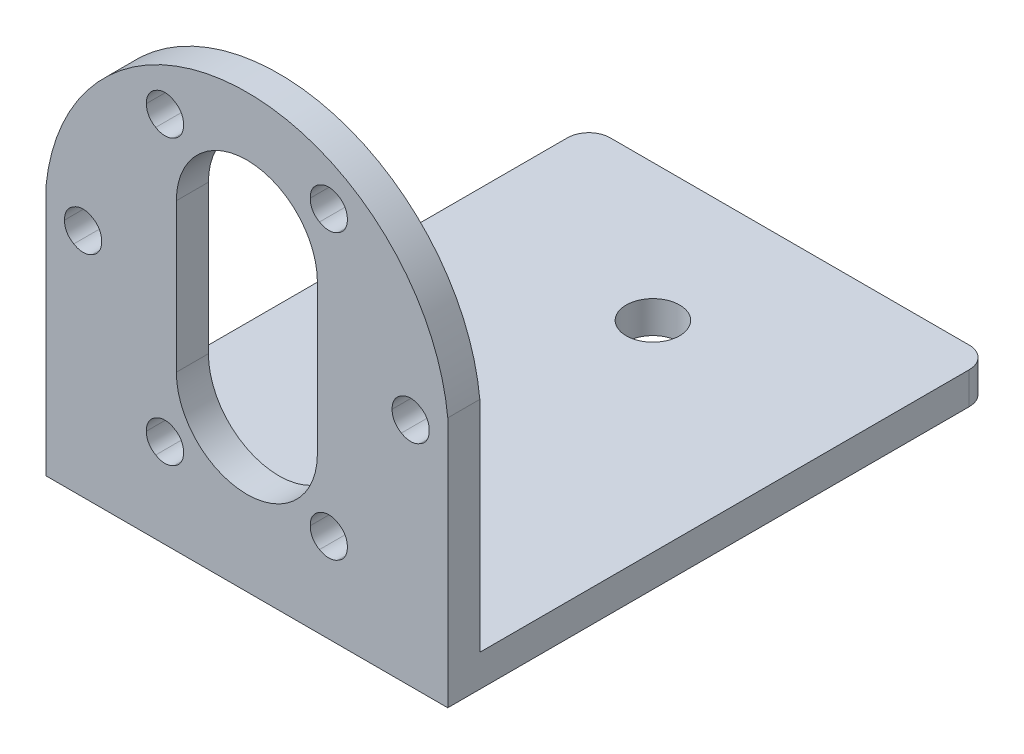
SolidWorks part; units mm, degrees
ref_plane "Front Plane" through (0, 0, 0) normal (0, 0, 1) x (1, 0, 0)
ref_plane "Top Plane" through (0, 0, 0) normal (0, 1, 0) x (1, 0, 0)
ref_plane "Right Plane" through (0, 0, 0) normal (1, 0, 0) x (0, 0, -1)
sketch "Sketch1" plane through (0, 0, 0) normal (0, 0, 1) x (1, 0, 0)
  line L0 (0, 0) -> (0, 39) construction
  line L1 (-18.8, 0) -> (18.8, 0)
  line L2 (-18.8, 0) -> (-18.8, 22)
  line L4 (18.8, 0) -> (18.8, 22)
  line L6 (-6.6, 12.9994) -> (-6.6, 26.8994)
  line L8 (6.6, 12.9994) -> (6.6, 26.8994)
  arc A0 (-18.8, 22) -> (18.8, 22) centre (0, 20.1047) cw
  arc A1 (-6.6, 26.8994) -> (6.6, 26.8994) centre (0, 26.9) cw
  arc A2 (-6.6, 12.9994) -> (6.6, 12.9994) centre (0, 13) ccw
  dimension "D3" = 39
  dimension "D5" = 27.1
  dimension "D6" = 5.5
  dimension "D1" = 37.6
  dimension "D2" = 22
  dimension "D4" = 13.2
  dimension "D7" = 13.9
extrude "Boss-Extrude1" add sketch "Sketch1" along normal blind 3
sketch "Sketch2" plane through (0, 0, 0) normal (0, -1, 0) x (1, 0, 0)
  line L0 (18.8, 3) -> (18.8, 0) construction
  line L1 (-18.8, 3) -> (18.8, 3)
  line L2 (-18.8, 3) -> (-18.8, -47.8)
  line L3 (-18.8, -47.8) -> (18.8, -47.8)
  line L4 (18.8, 3) -> (18.8, -47.8)
  dimension "D1" = 50.8
extrude "Boss-Extrude2" add sketch "Sketch2" against normal blind 1.5 and the other way blind 1.5
fillet "Fillet2" radius 2 2 edges at (-18.8, 0, -47.8) (18.8, 0, -47.8)
sketch "Sketch4" plane through (0, 0, 3) normal (0, 0, 1) x (1, 0, 0)
  line L0 (0, 0) -> (0, 39) construction
  line L1 (-7.6648, 33.2258) -> (-5.815, 30.0218) construction
  line L2 (-5.815, 30.0218) -> (0, 19.95) construction
  line L3 (0, 19.95) -> (-5.815, 9.8782) construction
  line L4 (0, 19.95) -> (5.815, 9.8782) construction
  line L5 (5.815, 9.8782) -> (7.6648, 6.6742) construction
  line L6 (0, 19.95) -> (5.815, 30.0218) construction
  line L7 (5.815, 30.0218) -> (7.6648, 33.2258) construction
  line L8 (-5.815, 9.8782) -> (-7.6648, 6.6742) construction
  line L9 (7.325, 33.2258) -> (7.6648, 33.2258) construction
  line L10 (7.6648, 33.2258) -> (9.5146, 36.4297) construction
  circle A0 centre (7.6648, 33.2258) radius 1.6
  arc A1 (18.8, 22) -> (-18.8, 22) centre (0, 20.1047) ccw construction
  circle A3 centre (15.3295, 19.95) radius 1.6
  circle A4 centre (7.6648, 6.6742) radius 1.6
  circle A5 centre (-7.6648, 6.6742) radius 1.6
  circle A6 centre (-15.3295, 19.95) radius 1.6
  circle A7 centre (-7.6648, 33.2258) radius 1.6
  arc A8 (-6.6, 12.9994) -> (6.6, 12.9994) centre (0, 13) ccw construction
  arc A9 (6.6, 26.8994) -> (-6.6, 26.8994) centre (0, 26.9) ccw construction
  point P26 (0, 19.95)
  dimension "D1" = 3.2
  dimension "D2" = 6
extrude "Cut-Extrude2" cut sketch "Sketch4" against normal up to next
pattern_circular "CirPattern1" count 6 over 360 about axis through (0, 20.1047, 3) along (0, 0, -1) of "Cut-Extrude2"
sketch "Szkic1" plane through (0, 1.5, 0) normal (0, 1, 0) x (1, 0, 0)
  line L0 (18.8, 0) -> (-18.8, 0) construction
  circle A0 centre (0, 15) radius 2.5
  circle A1 centre (0, 35) radius 2.5
  dimension "D1" = 5
  dimension "D2" = 5
  dimension "D3" = 20
  dimension "D4" = 15
extrude "Wytnij-wyciągnięcie1" cut sketch "Szkic1" against normal blind 10
sketch "Szkic2" plane through (0, 1.5, 0) normal (0, 1, 0) x (1, 0, 0)
  line L0 (-16.8, 47.8) -> (16.8, 47.8) construction
  line L1 (18.8, 0) -> (18.8, 47.8)
  line L2 (18.8, 47.8) -> (-18.8, 47.8)
  line L3 (-18.8, 0) -> (-18.8, 47.8)
  ellipse E0 centre (0, -45.5597) end of major axis (0, -138.9194) minor radius 21.5388 (18.8, 0) -> (-18.8, 0) ccw
